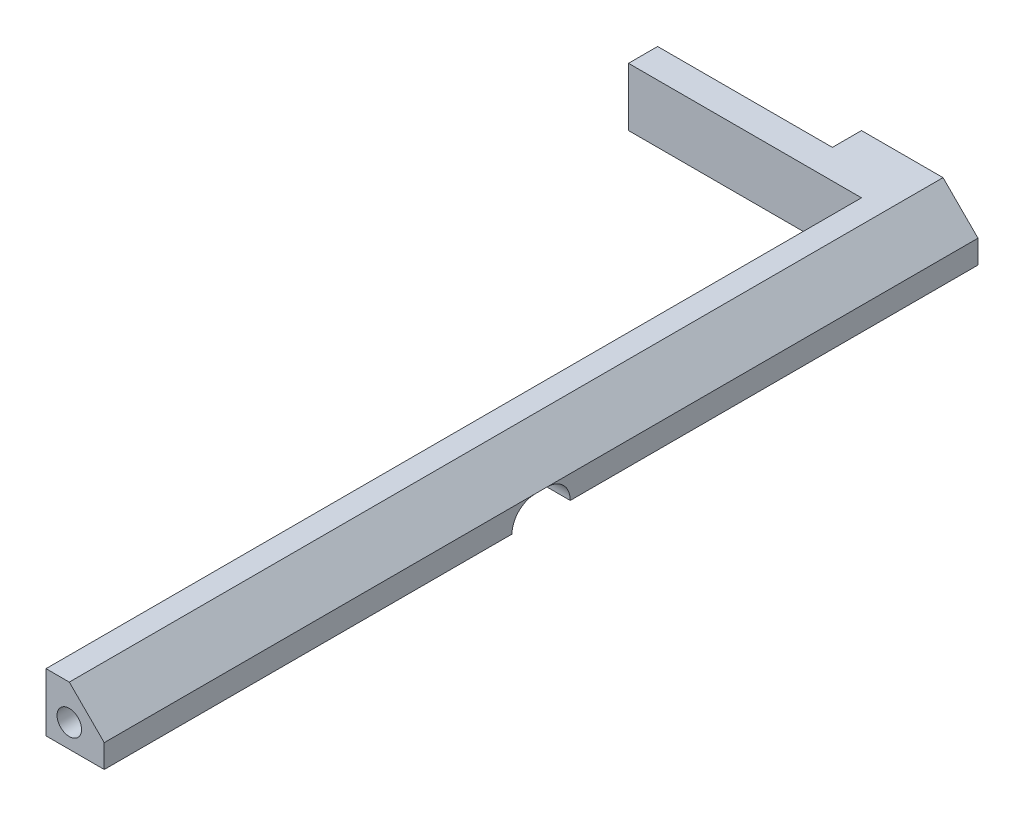
SolidWorks part; units mm, degrees
material "ABS"
ref_plane "Płaszczyzna przednia" through (0, 0, 0) normal (0, 0, 1) x (1, 0, 0)
ref_plane "Płaszczyzna górna" through (0, 0, 0) normal (0, 1, 0) x (1, 0, 0)
ref_plane "Płaszczyzna prawa" through (0, 0, 0) normal (1, 0, 0) x (0, 0, -1)
sketch "Szkic1" plane through (0, 0, 0) normal (0, 1, 0) x (1, 0, 0)
  line L0 (0, 0) -> (0, 150)
  line L1 (0, 150) -> (-20, 150)
  line L2 (-20, 150) -> (-20, 145)
  line L5 (-50, 140) -> (-10, 140)
  line L6 (-10, 140) -> (-10, 0)
  line L7 (-10, 0) -> (0, 0)
  line L8 (-50, 140) -> (-50, 145)
  line L9 (-50, 145) -> (-20, 145)
  dimension "D1" = 5
  dimension "D5" = 10
  dimension "D6" = 140
  dimension "D2" = 20
  dimension "D3" = 30
  dimension "D4" = 5
extrude "Dodanie-wyciągnięcie1" add sketch "Szkic1" along normal blind 10
sketch "Szkic2" plane through (0, 0, 0) normal (0, -1, 0) x (1, 0, 0)
  line L0 (0, 0) -> (0, -27) construction
  line L1 (0, 0) -> (0, -150) construction
  line L2 (0, -27) -> (-7.2, -27) construction
  line L3 (-7.2, -27) -> (-7.2, -123) construction
  circle A0 centre (-7.2, -123) radius 2.1
  circle A1 centre (-7.2, -27) radius 2.1
  dimension "D4" = 4.2
  dimension "D5" = 4.2
  dimension "D1" = 27
  dimension "D2" = 7.2
  dimension "D3" = 96
extrude "Wytnij-wyciągnięcie1" cut sketch "Szkic2" against normal blind 4
sketch "Szkic3" plane through (0, 0, 0) normal (0, 0, 1) x (1, 0, 0)
  line L0 (0, 0) -> (-6, 0) construction
  line L1 (-10, 0) -> (0, 0) construction
  line L2 (-6, 0) -> (-6, 4) construction
  circle A0 centre (-6, 4) radius 2.1
  dimension "D3" = 4.2
  dimension "D1" = 6
  dimension "D2" = 4
extrude "Wytnij-wyciągnięcie2" cut sketch "Szkic3" against normal blind 4
chamfer "Sfazowanie1" distance 6 angle 45 1 edges at (0, 10, -75)
sketch "Szkic4" plane through (0, 0, 0) normal (0, -1, 0) x (1, 0, 0)
  line L0 (0, 0) -> (0, -75) construction
  line L1 (0, 0) -> (0, -150) construction
  line L7 (0, -80) -> (0, -70)
  line L8 (0, -70) -> (-10, -70)
  line L9 (-10, -140) -> (-10, 0) construction
  line L10 (-10, -70) -> (-10, -80)
  line L11 (-10, -80) -> (0, -80)
  point P8 (0, -75)
  dimension "D1" = 75
  dimension "D2" = 10
extrude "Wytnij-wyciągnięcie3" cut sketch "Szkic4" against normal blind 4
fillet "Zaokrąglenie1" radius 4 2 edges at (-5, 4, -80) (-5, 4, -70)
equation "\"Lenght\"=140"
equation "\"Width\"=10"
equation "\"D5@Szkic1\"=\"Width\""
equation "\"D6@Szkic1\"=\"Lenght\""
equation "\"D4@Szkic1\"=\"Width\"/2"
equation "\"D1@Szkic1\"=\"Width\"/2"
equation "\"D1@Szkic2\"=(\"Lenght\"+\"Width\"-96)/2"
equation "\"InsertDiameter\"=4.2"
equation "\"D5@Szkic2\"=\"InsertDiameter\""
equation "\"D4@Szkic2\"=\"InsertDiameter\""
equation "\"D3@Szkic3\"=\"InsertDiameter\""
equation "\"D1@Szkic3\"=\"Width\"/2+1"
equation "\"D2@Szkic3\"=\"Width\"/2-1"
equation "\"D1@Szkic4\"=(\"Lenght\"+\"Width\")/2"
equation "\"D2@Szkic4\"=\"Width\""
